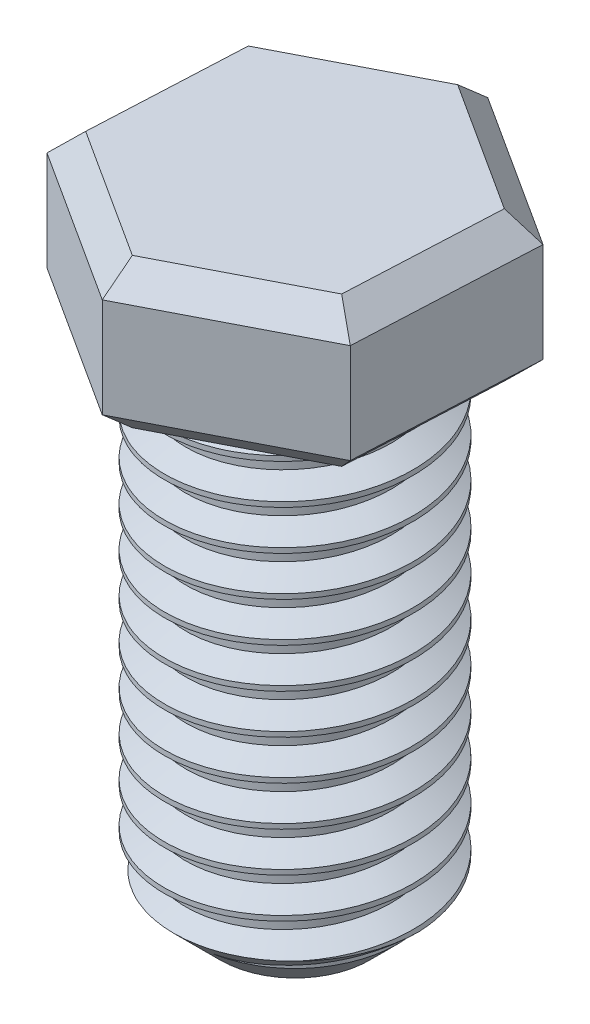
SolidWorks part; units mm, degrees
ref_plane "Front" through (0, 0, 0) normal (0, 0, 1) x (1, 0, 0)
ref_plane "Top" through (0, 0, 0) normal (0, 1, 0) x (1, 0, 0)
ref_plane "Right" through (0, 0, 0) normal (1, 0, 0) x (0, 0, -1)
sketch "Sketch1" plane through (0, 0, 0) normal (0, 1, 0) x (1, 0, 0)
  circle A0 centre (0, 0) radius 2.5
extrude "Boss-Extrude1" add sketch "Sketch1" along normal blind 10
chamfer "Chamfer2" distance 1 angle 45 1 edges at (0, 0, 2.5)
thread "Thread1" pitch 0.8 method cut profile "Thread Profile1" start angle 0, offset 1, length 12, pitch 0.8, diameter 5
ref_plane "Plane1" through (-2.5, 11, 0) normal (0, 0, 1) x (-1, 0, 0)
sketch "Thread Profile1" plane through (-2.5, 11, 0) normal (0, 0, 1) x (-1, 0, 0)
  line L0 (0, 0) -> (0, 0.8) construction
  line L11 (0, 0) -> (0, 0.7)
  line L12 (0, 0.7) -> (-0.433, 0.45)
  line L13 (-0.433, 0.45) -> (-0.433, 0.25)
  line L15 (-0.433, 0.25) -> (0, 0)
  line L17 (-0.433, 0.35) -> (0, 0.35) construction
  point P2 (0, 0)
  dimension "Pitch" = 0.8
  dimension "Profile_Angle" = 60
  dimension "Profile_Land" = 0.2
  dimension "Profile_Height" = 0.433
sketch "Sketch4" plane through (0, 10, 0) normal (0, 1, 0) x (1, 0, 0)
  line L1 (0.177, 3.6958) -> (-3.1121, 2.0011)
  line L2 (-3.1121, 2.0011) -> (-3.2891, -1.6946)
  line L3 (-3.2891, -1.6946) -> (-0.177, -3.6958)
  line L4 (-0.177, -3.6958) -> (3.1121, -2.0011)
  line L5 (3.1121, -2.0011) -> (3.2891, 1.6946)
  line L6 (3.2891, 1.6946) -> (0.177, 3.6958)
  circle A0 centre (0, 0) radius 3.7 construction
  circle A1 centre (0, 0) radius 3.2043 construction
  point P3 (3.2891, 1.6946)
extrude "Boss-Extrude2" add sketch "Sketch4" along normal blind 3
chamfer "Chamfer1" distance 0.5 angle 45 12 edges at (3.2006, 13, 0.1533) (1.4676, 13, 2.8485) (-1.733, 13, 2.6952) (-3.2006, 13, -0.1533) (-1.4676, 13, -2.8485) (1.733, 13, -2.6952) (-1.733, 10, 2.6952) (-3.2006, 10, -0.1533) (-1.4676, 10, -2.8485) (1.4676, 10, 2.8485) (3.2006, 10, 0.1533) (1.733, 10, -2.6952)
